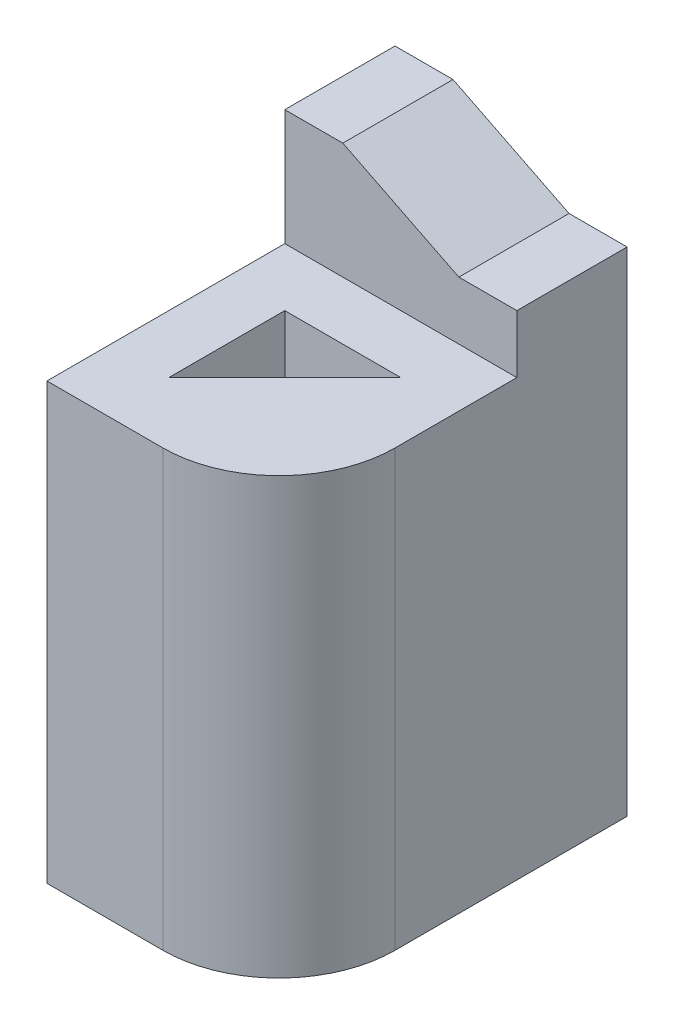
SolidWorks part; units mm, degrees
ref_plane "Front Plane" through (0, 0, 0) normal (0, 0, 1) x (1, 0, 0)
ref_plane "Top Plane" through (0, 0, 0) normal (0, 1, 0) x (1, 0, 0)
ref_plane "Right Plane" through (0, 0, 0) normal (1, 0, 0) x (0, 0, -1)
sketch "Sketch1" plane through (0, 0, 0) normal (0, 1, 0) x (1, 0, 0)
  line L0 (0, 0) -> (0, -1524)
  line L1 (0, -1524) -> (508, -1524)
  line L2 (1016, -1016) -> (1016, 0)
  line L3 (1016, 0) -> (0, 0)
  line L4 (0, -482.6) -> (1016, -482.6)
  line L5 (254, -736.6) -> (762, -736.6)
  line L6 (762, -736.6) -> (254, -1244.6)
  line L7 (254, -1244.6) -> (254, -736.6)
  arc A0 (508, -1524) -> (1016, -1016) centre (508, -1016) ccw
  dimension "D8" = 508
  dimension "D1" = 1016
  dimension "D2" = 1524
  dimension "D3" = 482.6
  dimension "D4" = 508
  dimension "D5" = 508
  dimension "D6" = 254
  dimension "D7" = 254
extrude "Boss-Extrude1" add sketch "Sketch1" along normal blind 1905 contours L1 A0 L2 L4 L0 L6 L7 L5 region at (508, 0, 497.1491)
extrude "Boss-Extrude2" add sketch "Sketch1<3>" along normal blind 2413 contours L0 L4 L2 L3 region at (508, 0, 241.3)
sketch "Sketch1<3>" plane through (0, 0, 0) normal (0, 1, 0) x (1, 0, 0) same geometry as "Sketch1"
sketch "Sketch2" plane through (0, 0, 482.6) normal (0, 0, 1) x (1, 0, 0)
  line L0 (254, 2413) -> (762, 2159)
  line L1 (0, 2413) -> (1016, 2413) construction
  line L2 (762, 2159) -> (1016, 2159)
  line L3 (1016, 2413) -> (1016, 1905) construction
  line L4 (1016, 2159) -> (1016, 2413)
  line L5 (1016, 2413) -> (254, 2413)
  dimension "D1" = 508
  dimension "D2" = 254
  dimension "D3" = 254
extrude "Cut-Extrude1" cut sketch "Sketch2" against normal blind 482.6
